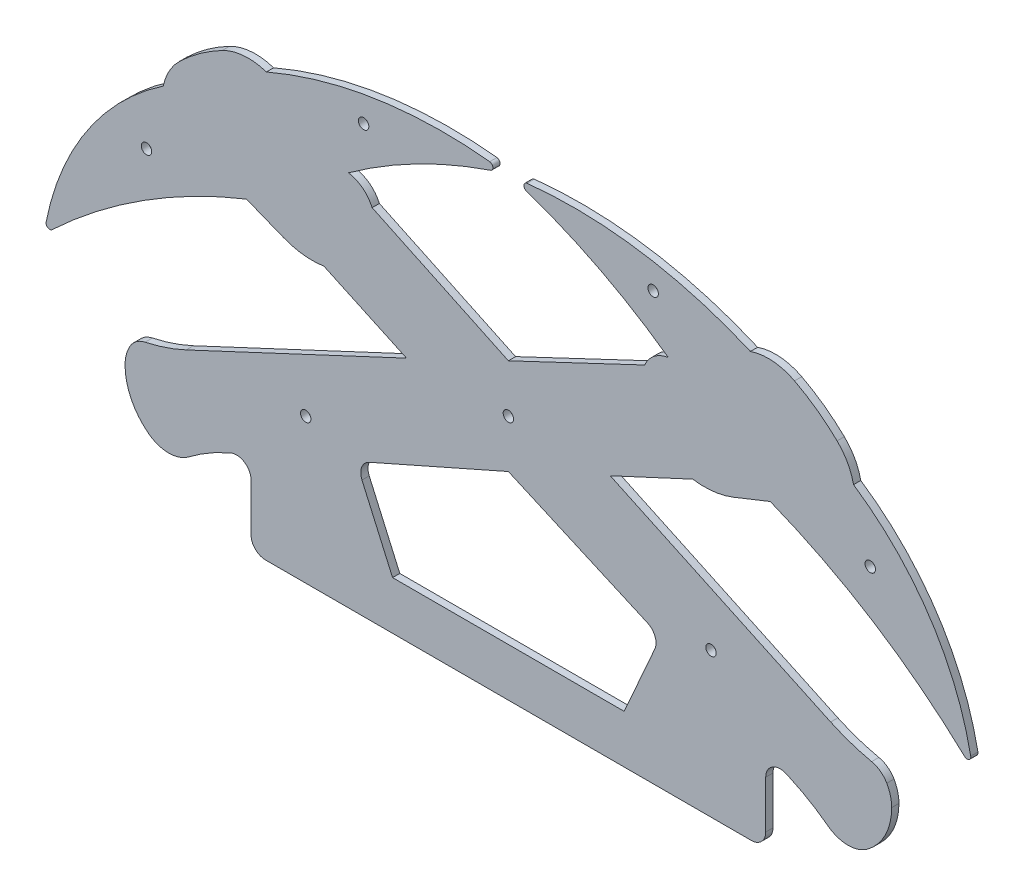
SolidWorks part; units mm, degrees
ref_plane "Front Plane" through (0, 0, 0) normal (0, 0, 1) x (1, 0, 0)
ref_plane "Top Plane" through (0, 0, 0) normal (0, 1, 0) x (1, 0, 0)
ref_plane "Right Plane" through (0, 0, 0) normal (1, 0, 0) x (0, 0, -1)
sketch "Sketch1" plane through (0, 0, 0) normal (0, 0, 1) x (1, 0, 0)
  line L0 (-7.456, 89.4504) -> (178.8798, 89.4504) construction
  line L1 (192.9838, 175.4412) -> (96.3096, 130.2274)
  line L2 (114.7894, 100.3711) -> (237.664, 154.6988)
  line L3 (237.664, 196.7769) -> (177.8969, 225.0593)
  line L4 (192.9838, 175.4412) -> (156.7682, 192.2435)
  line L5 (122.7816, 200.7534) -> (138.9317, 194.3128)
  line L6 (237.664, 267.4202) -> (237.664, 154.6988) construction
  line L7 (352.5463, 200.7534) -> (336.3962, 194.3128)
  line L8 (282.3442, 175.4412) -> (318.5597, 192.2435)
  line L9 (237.664, 196.7769) -> (297.431, 225.0593)
  line L10 (360.5386, 100.3711) -> (237.664, 154.6988)
  line L11 (282.3442, 175.4412) -> (379.0184, 130.2274)
  arc A0 (96.3096, 130.2274) -> (78.3175, 124.1761) centre (60.6568, 206.4587) cw
  arc A1 (78.3175, 124.1761) -> (71.6647, 119.2855) centre (80.4305, 114.3314) ccw
  arc A2 (71.6647, 119.2855) -> (69.5125, 111.0967) centre (86.1425, 111.1032) ccw
  arc A3 (69.5125, 111.0967) -> (79.9352, 90.1473) centre (95.7986, 111.107) ccw
  arc A4 (79.9352, 90.1473) -> (97.4231, 90.1473) centre (88.6791, 101.7003) ccw
  arc A5 (97.4231, 90.1473) -> (114.7894, 100.3711) centre (150.0582, 20.6026) cw
  arc A6 (156.7682, 192.2435) -> (138.9317, 194.3128) centre (151.678, 226.2747) cw
  arc A7 (307.7941, 233.1357) -> (297.431, 225.0593) centre (310.0373, 219.5707) ccw
  arc A8 (122.7816, 200.7534) -> (34.0226, 143.1916) centre (222.9286, -50.884) ccw
  arc A9 (34.0226, 143.1916) -> (86.2485, 225.4232) centre (153.9924, 124.6982) cw
  arc A10 (86.2485, 225.4232) -> (93.4631, 238.4495) centre (110.9979, 220.2268) cw
  arc A11 (93.4631, 238.4495) -> (112.1407, 251.9085) centre (149.9585, 179.7377) cw
  arc A12 (112.1407, 251.9085) -> (131.4929, 253.4154) centre (123.5746, 230.0882) cw
  arc A15 (167.5338, 233.1357) -> (177.8969, 225.0593) centre (165.2907, 219.5707) cw
  arc A18 (363.1873, 251.9085) -> (343.835, 253.4154) centre (351.7533, 230.0882) ccw
  arc A19 (381.8648, 238.4495) -> (363.1873, 251.9085) centre (325.3694, 179.7377) ccw
  arc A20 (389.0794, 225.4232) -> (381.8648, 238.4495) centre (364.3301, 220.2268) ccw
  arc A21 (441.3053, 143.1916) -> (389.0794, 225.4232) centre (321.3356, 124.6982) ccw
  arc A22 (352.5463, 200.7534) -> (441.3053, 143.1916) centre (252.3994, -50.884) cw
  arc A23 (318.5597, 192.2435) -> (336.3962, 194.3128) centre (323.6499, 226.2747) ccw
  arc A24 (377.9048, 90.1473) -> (360.5386, 100.3711) centre (325.2698, 20.6026) ccw
  arc A25 (395.3928, 90.1473) -> (377.9048, 90.1473) centre (386.6488, 101.7003) cw
  arc A26 (405.8155, 111.0967) -> (395.3928, 90.1473) centre (379.5293, 111.107) cw
  arc A27 (403.6633, 119.2855) -> (405.8155, 111.0967) centre (389.1855, 111.1032) cw
  arc A28 (397.0105, 124.1761) -> (403.6633, 119.2855) centre (394.8975, 114.3314) cw
  arc A29 (379.0184, 130.2274) -> (397.0105, 124.1761) centre (414.6711, 206.4587) ccw
  arc A30 (167.5338, 233.1357) -> (236.5684, 267.4202) centre (306.6135, 39.7332) cw
  arc A31 (131.4929, 253.4154) -> (236.5684, 267.4202) centre (208.8369, 74.3006) cw
  arc A32 (307.7941, 233.1357) -> (238.7596, 267.4202) centre (168.7145, 39.7332) ccw
  arc A33 (343.835, 253.4154) -> (238.7596, 267.4202) centre (266.491, 74.3006) ccw
extrude "Boss-Extrude1" add sketch "Sketch1" along normal blind 3.175
sketch "Sketch2" plane through (0, 0, 0) normal (0, 0, 1) x (1, 0, 0)
  line L0 (124.7751, 104.7862) -> (124.7751, 67.8337)
  line L1 (124.7751, 67.8337) -> (350.5529, 67.8337)
  line L2 (237.664, 89.0003) -> (237.664, 67.8337) construction
  line L3 (288.464, 89.0003) -> (186.864, 89.0003)
  line L4 (186.864, 89.0003) -> (170.8729, 125.1679)
  line L5 (114.7894, 100.3711) -> (237.664, 154.6988) construction
  line L6 (124.7751, 104.7862) -> (170.8729, 125.1679)
  line L7 (350.5529, 104.7862) -> (304.4551, 125.1679)
  line L8 (288.464, 89.0003) -> (304.4551, 125.1679)
  line L9 (350.5529, 104.7862) -> (350.5529, 67.8337)
  line L10 (237.664, 154.6988) -> (360.5386, 100.3711) construction
  arc A3 (79.9352, 90.1473) -> (97.4231, 90.1473) centre (88.6791, 101.7003) ccw construction
  dimension "D1" = 21.1667
  dimension "D2" = 12.7
  dimension "D3" = 225.7778
  dimension "D4" = 50.8
extrude "Boss-Extrude2" add sketch "Sketch2" along normal up to surface (3.175 mm away) up to face at (237.664, 178.0943, 3.175)
fillet "Fillet1" radius 6.35 6 edges at (350.5529, 67.8337, 1.5875) (304.4551, 125.1679, 1.5875) (170.8729, 125.1679, 1.5875) (124.7751, 67.8337, 1.5875) (350.5529, 104.7862, 1.5875) (124.7751, 104.7862, 1.5875)
sketch "Sketch3" plane through (0, 0, 3.175) normal (0, 0, 1) x (1, 0, 0)
  line L0 (237.664, 196.7769) -> (237.664, 154.6988) construction
  line L1 (78.914, 197.9629) -> (396.414, 197.9629) construction
  line L2 (301.164, 255.1129) -> (174.164, 255.1129) construction
  line L3 (148.764, 131.2879) -> (326.564, 131.2879) construction
  circle A0 centre (237.664, 175.7379) radius 2.286
  circle A1 centre (78.914, 197.9629) radius 2.286
  circle A2 centre (174.164, 255.1129) radius 2.286
  circle A3 centre (301.164, 255.1129) radius 2.286
  circle A4 centre (396.414, 197.9629) radius 2.286
  circle A5 centre (148.764, 131.2879) radius 2.286
  circle A6 centre (326.564, 131.2879) radius 2.286
  point P14 (237.664, 255.1129)
  point P15 (237.664, 197.9629)
  point P18 (237.664, 131.2879)
  dimension "D1" = 4.572
  dimension "D2" = 127
  dimension "D3" = 317.5
  dimension "D4" = 22.225
  dimension "D5" = 79.375
  dimension "1.75" = 44.45
  dimension "D7" = 177.8
extrude "Cut-Extrude1" cut sketch "Sketch3" against normal through all
fillet "Fillet2" radius 1.5875 4 edges at (34.0226, 143.1916, 1.5875) (441.3053, 143.1916, 1.5875) (238.7596, 267.4202, 1.5875) (236.5684, 267.4202, 1.5875)
scale "Scale4" scale about centroid uniform scaling yes scale factor 0.9
scale "Scale5" [suppressed]
